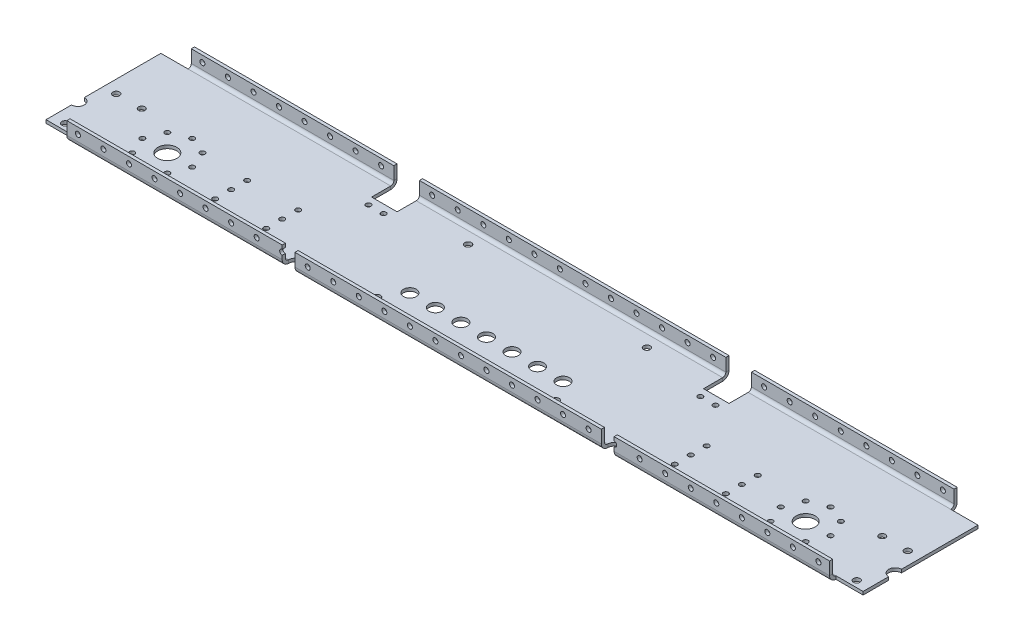
SolidWorks part; units mm, degrees
note: The reader was unsure of these and kept them because the rebuilt part matched: thickness of "Base-Flange1", "Edge-Flange1", "Sheet-Metal1", "Sheet-Metal2", "Sheet-Metal9", "Sheet-Metal10", "Sheet-Metal11", "Sheet-Metal12", "Sheet-Metal13", "Sheet-Metal14", "Sheet-Metal15", "Sheet-Metal16", "Sheet-Metal17", "Sheet-Metal18", "Sheet-Metal19", "Sheet-Metal20", "Sheet-Metal21"; flange length of "Edge-Flange1".
ref_plane "Front Plane" through (0, 0, 0) normal (0, 0, 1) x (1, 0, 0)
ref_plane "Top Plane" through (0, 0, 0) normal (0, 1, 0) x (1, 0, 0)
ref_plane "Right Plane" through (0, 0, 0) normal (1, 0, 0) x (0, 0, -1)
sketch "Sketch1" plane through (0, 0, 0) normal (0, 1, 0) x (1, 0, 0)
  line L1 (406.4, -63.5) -> (-406.4, -63.5)
  line L2 (406.4, -63.5) -> (406.4, 63.5)
  line L3 (406.4, 63.5) -> (-406.4, 63.5)
  line L4 (-406.4, -63.5) -> (-406.4, 63.5)
  line L5 (406.4, -63.5) -> (-406.4, 63.5) construction
  line L6 (406.4, 63.5) -> (-406.4, -63.5) construction
  point P0 (0, 0)
  dimension "D1" = 127
  dimension "D2" = 812.8
base flange "Base-Flange1" sketch "Sketch1" thickness 3.175 reverse thickness direction no parameters "D1"=1
edge flange "Edge-Flange1" sketch "Sketch23" flange profiles "Sketch23", "Sketch25" flange angle 90 flange length 19.05 flange position material inside bend radius 3.175 thickness 3.175 relief rectangular parameters "D6"=10, "D8"=1
bend "EdgeBend1" bend radius 3.175 bend angle 90 parameters "D5"=1
bend "EdgeBend2" bend radius 3.175 bend angle 90 parameters "D5"=2
sketch "Sketch23" plane through (0, 0, -63.5) normal (0, 0, -1) x (-1, 0, 0)
  line L0 (-406.4, 0) -> (406.4, 0) construction
  line L1 (-406.4, 0) -> (406.4, 0)
  line L2 (-406.4, 0) -> (-406.4, 15.875)
  line L3 (-406.4, 15.875) -> (406.4, 15.875)
  line L4 (406.4, 15.875) -> (406.4, 0)
sketch "Sketch25" plane through (0, 0, 63.5) normal (0, 0, 1) x (1, 0, 0)
  line L0 (-406.4, 0) -> (406.4, 0) construction
  line L1 (-406.4, 0) -> (406.4, 0)
  line L2 (-406.4, 0) -> (-406.4, 15.875)
  line L3 (-406.4, 15.875) -> (406.4, 15.875)
  line L4 (406.4, 15.875) -> (406.4, 0)
hole_wizard "Mounting Holes" positions "Sketch19" profile "Sketch20" hole size "Ø5.0" standard "ANSI Metric" end condition through all
sketch "Sketch19" plane through (342.9, 0, -63.5) normal (0, 0, 1) x (1, 0, 0)
  line L0 (63.5, 9.525) -> (-749.3, 9.525) construction
  line L3 (63.5, 15.875) -> (63.5, 3.175) construction
  point P9 (-736.6, 9.525)
  dimension "D1" = 12.7
sketch "Sketch20" plane through (-393.7, 9.525, -63.5) normal (1, 0, 0) x (0, 1, 0)
  line L0 (0, 0) -> (0, 127)
  line L1 (0, 127) -> (2.5, 127)
  line L2 (2.5, 127) -> (2.5, 0)
  line L5 (2.5, 0) -> (0, 0)
  line L11 (0, -6.35) -> (0, 107.95) construction
  dimension "Thru Hole Dia." = 5
  dimension "Thru Hole Depth" = 127
pattern_linear "LPattern3" count 32 spacing 25.4 along (1, 0, 0) of "Mounting Holes"
sketch "Sketch21" plane through (0, -3.175, 0) normal (0, -1, 0) x (1, 0, 0)
  line L0 (406.4, 0) -> (177.8, 0) construction
  line L1 (406.4, 63.5) -> (-406.4, 63.5) construction
  line L2 (-406.4, -57.15) -> (-379.349, -57.15)
  line L3 (177.8, -38.1) -> (152.4, -38.1)
  line L4 (177.8, -38.1) -> (177.8, -63.5)
  line L5 (177.8, -63.5) -> (152.4, -63.5)
  line L6 (152.4, -38.1) -> (152.4, -63.5)
  line L7 (-177.8, 0) -> (-406.4, 0) construction
  line L8 (-152.4, -63.5) -> (-177.8, -63.5)
  line L9 (-152.4, -63.5) -> (-152.4, -38.1)
  line L10 (-152.4, -38.1) -> (-177.8, -38.1)
  line L11 (-177.8, -63.5) -> (-177.8, -38.1)
  line L12 (-406.4, -57.15) -> (-406.4, 57.15) construction
  line L13 (406.4, 57.15) -> (406.4, -57.15) construction
  line L14 (-406.4, -63.5) -> (406.4, -63.5) construction
  line L16 (-406.4, -57.15) -> (-406.4, -63.5)
  line L17 (-406.4, -63.5) -> (-379.349, -63.5)
  line L18 (-379.349, -57.15) -> (-379.349, -63.5)
  line L19 (-406.4, 57.15) -> (-379.349, 57.15)
  line L20 (-406.4, 57.15) -> (-406.4, 63.5)
  line L21 (-406.4, 63.5) -> (-379.349, 63.5)
  line L22 (-379.349, 57.15) -> (-379.349, 63.5)
  line L23 (379.349, -57.15) -> (379.349, 57.15) construction
  line L24 (406.4, -57.15) -> (379.349, -57.15)
  line L25 (406.4, -57.15) -> (406.4, -63.5)
  line L26 (406.4, -63.5) -> (379.349, -63.5)
  line L27 (379.349, -57.15) -> (379.349, -63.5)
  line L28 (406.4, 57.15) -> (379.349, 57.15)
  line L29 (406.4, 57.15) -> (406.4, 63.5)
  line L30 (406.4, 63.5) -> (379.349, 63.5)
  line L31 (379.349, 57.15) -> (379.349, 63.5)
  dimension "D1" = 228.6
  dimension "D2" = 27.051
  dimension "D3" = 25.4
  dimension "D4" = 25.4
extrude "Cut-Extrude3" cut sketch "Sketch21" against normal through all normal cut yes
sketch "Sketch26" plane through (0, 0, 0) normal (0, 1, 0) x (1, 0, 0)
  line L0 (379.349, -57.15) -> (-379.349, -57.15) construction
  line L1 (152.4, -57.15) -> (152.4, -63.5)
  line L2 (379.349, -63.5) -> (-379.349, -63.5) construction
  line L3 (152.4, -63.5) -> (165.1, -63.5)
  line L4 (165.1, -63.5) -> (165.1, -57.15)
  line L5 (-165.1, -57.15) -> (-165.1, -63.5)
  line L6 (-165.1, -63.5) -> (-152.4, -63.5)
  line L7 (-152.4, -63.5) -> (-152.4, -57.15)
  line L12 (0, 158.0045) -> (0, -158.0045) construction
  line L13 (152.4, -63.5) -> (-152.4, -63.5) construction
  arc A0 (-165.1, -57.15) -> (-152.4, -57.15) centre (-158.75, -57.15) cw
  arc A1 (152.4, -57.15) -> (165.1, -57.15) centre (158.75, -57.15) cw
  point P26 (0, 0)
  point P29 (0, -63.5)
  dimension "D2" = 6.35
  dimension "D1" = 304.8
extrude "Cut-Extrude4" cut sketch "Sketch26" against normal through all both and the other way through all
hole_wizard "80/20 Connection Holes" positions "Sketch27" profile "Sketch28" hole size "Ø6.0" standard "ANSI Metric" end condition through all
sketch "Sketch27" plane through (0, 0, 0) normal (0, 1, 0) x (1, 0, 0)
  line L1 (-393.7, 0) -> (-393.7, -50.8) construction
  line L3 (393.7, -50.8) -> (393.7, 0) construction
  line L4 (406.4, -57.15) -> (406.4, 57.15) construction
  line L5 (393.7, -25.4) -> (406.4, -25.4) construction
  line L7 (-393.7, -25.4) -> (-406.4, -25.4) construction
  line L8 (-406.4, 57.15) -> (-406.4, -57.15) construction
  line L10 (393.7, -50.8) -> (393.7, -57.15) construction
  line L11 (379.349, -57.15) -> (165.1, -57.15) construction
  line L13 (-393.7, -50.8) -> (-393.7, -57.15) construction
  line L14 (-165.1, -57.15) -> (-379.349, -57.15) construction
  line L15 (406.4, -57.15) -> (379.349, -57.15) construction
  point P10 (-393.7, 0)
  point P11 (-393.7, -50.8)
  point P14 (393.7, -50.8)
  point P15 (393.7, 0)
  dimension "D1" = 31.75
  dimension "D5" = 12.7
  dimension "D6" = 50.8
sketch "Sketch28" plane through (-393.7, 0, 0) normal (1, 0, 0) x (0, 0, 1)
  line L0 (0, 0) -> (0, 3.175)
  line L1 (0, 3.175) -> (3.3, 3.175)
  line L2 (3.3, 3.175) -> (3.3, 0)
  line L5 (3.3, 0) -> (0, 0)
  line L11 (0, -6.35) -> (0, 107.95) construction
  dimension "Thru Hole Dia." = 6.6
  dimension "Thru Hole Depth" = 3.175
hole_wizard "Motor Holes" positions "Sketch29" profile "Sketch30" hole size "3/4" standard "ANSI Inch" end condition through all
sketch "Sketch29" plane through (0, 0, 0) normal (0, 1, 0) x (1, 0, 0)
  line L0 (-165.1, -63.5) -> (-379.349, -63.5) construction
  line L1 (-317.5, -25.4) -> (317.5, -25.4) construction
  line L3 (0, 0) -> (0, -25.4) construction
  line L5 (-406.4, 57.15) -> (-406.4, -57.15) construction
  point P0 (-317.5, -25.4)
  point P2 (317.5, -25.4)
  dimension "D1" = 38.1
  dimension "D2" = 88.9
sketch "Sketch30" plane through (-317.5, 0, 25.4) normal (1, 0, 0) x (0, 0, 1)
  line L0 (0, 0) -> (0, 3.175)
  line L1 (0, 3.175) -> (9.525, 3.175)
  line L2 (9.525, 3.175) -> (9.525, 0)
  line L5 (9.525, 0) -> (0, 0)
  line L11 (0, -6.35) -> (0, 107.95) construction
  dimension "Thru Hole Dia." = 19.05
  dimension "Thru Hole Depth" = 3.175
hole_wizard "1/2 (0.5) Diameter Hole1" positions "Sketch31" profile "Sketch32" hole size "1/2" standard "ANSI Inch" end condition through all
sketch "Sketch31" plane through (0, 0, 0) normal (0, 1, 0) x (1, 0, 0)
  line L0 (0, 0) -> (0, -25.4) construction
  line L2 (0, -25.4) -> (-25.4, -25.4) construction
  line L3 (-25.4, -25.4) -> (-50.8, -25.4) construction
  line L4 (-50.8, -25.4) -> (-76.2, -25.4) construction
  line L6 (0, -25.4) -> (25.4, -25.4) construction
  line L7 (25.4, -25.4) -> (50.8, -25.4) construction
  line L8 (50.8, -25.4) -> (76.2, -25.4) construction
  line L9 (152.4, -63.5) -> (-152.4, -63.5) construction
  point P2 (0, -25.4)
  point P8 (-25.4, -25.4)
  point P10 (-50.8, -25.4)
  point P12 (-76.2, -25.4)
  point P17 (25.4, -25.4)
  point P19 (50.8, -25.4)
  point P21 (76.2, -25.4)
  dimension "D1" = 25.4
  dimension "D2" = 38.1
sketch "Sketch32" plane through (76.2, 0, 25.4) normal (1, 0, 0) x (0, 0, 1)
  line L0 (0, 0) -> (0, 3.175)
  line L1 (0, 3.175) -> (6.35, 3.175)
  line L2 (6.35, 3.175) -> (6.35, 0)
  line L5 (6.35, 0) -> (0, 0)
  line L11 (0, -6.35) -> (0, 107.95) construction
  dimension "Thru Hole Dia." = 12.7
  dimension "Thru Hole Depth" = 3.175
sketch "Sketch33" plane through (0, 0, 0) normal (0, 1, 0) x (1, 0, 0)
  line L0 (-406.4, -63.5) -> (-406.4, -25.4) construction
  line L1 (-406.4, 57.15) -> (-406.4, -57.15) construction
  line L2 (-406.4, -19.05) -> (-406.4, -31.75)
  line L3 (406.4, -63.5) -> (406.4, -25.4) construction
  line L4 (406.4, -57.15) -> (406.4, 57.15) construction
  line L5 (406.4, -19.05) -> (406.4, -31.75)
  line L6 (-406.4, -63.5) -> (-379.349, -63.5) construction
  line L7 (379.349, -63.5) -> (406.4, -63.5) construction
  arc A0 (-406.4, -19.05) -> (-406.4, -31.75) centre (-406.4, -25.4) cw
  arc A1 (406.4, -19.05) -> (406.4, -31.75) centre (406.4, -25.4) ccw
  dimension "D1" = 6.35
  dimension "D2" = 38.1
extrude "Cut-Extrude5" cut sketch "Sketch33" against normal through all
hole_wizard "Churrow Holes" positions "Sketch34" profile "Sketch35" hole size "Ø1.0" standard "ANSI Metric" end condition through all
sketch "Sketch34" plane through (0, 0, 0) normal (0, 1, 0) x (1, 0, 0)
  line L0 (-165.1, 50.8) -> (-88.9, 50.8) construction
  line L1 (-88.9, 50.8) -> (-88.9, -63.5) construction
  line L3 (152.4, -63.5) -> (-152.4, -63.5) construction
  line L4 (165.1, 50.8) -> (88.9, 50.8) construction
  line L5 (88.9, 50.8) -> (88.9, -63.5) construction
  line L6 (-88.9, 45.28) -> (88.9, 45.28) construction
  line L8 (-88.9, -45.28) -> (88.9, -45.28) construction
  line L9 (-152.4, 63.5) -> (152.4, 63.5) construction
  line L10 (-165.1, 50.8) -> (-165.1, 38.1) construction
  line L11 (-177.8, 38.1) -> (-152.4, 38.1) construction
  line L13 (165.1, 50.8) -> (165.1, 38.1) construction
  line L14 (152.4, 38.1) -> (177.8, 38.1) construction
  point P16 (-88.9, 45.28)
  point P18 (-88.9, -45.28)
  point P22 (88.9, 45.28)
  point P25 (88.9, -45.28)
  dimension "D1" = 76.2
  dimension "D2" = 18.22
  dimension "D3" = 18.22
sketch "Sketch35" plane through (88.9, 0, 45.28) normal (1, 0, 0) x (0, 0, 1)
  line L0 (0, 0) -> (0, 3.175)
  line L1 (0, 3.175) -> (3.3, 3.175)
  line L2 (3.3, 3.175) -> (3.3, 0)
  line L5 (3.3, 0) -> (0, 0)
  line L11 (0, -6.35) -> (0, 107.95) construction
  dimension "Thru Hole Dia." = 6.6
  dimension "Thru Hole Depth" = 3.175
hole_wizard "80/20 Support Holes" positions "Sketch40" profile "Sketch39" hole size "Ø5.0" standard "ANSI Metric" end condition through all
sketch "Sketch40" plane through (0, 0, 0) normal (0, 1, 0) x (1, 0, 0)
  line L0 (-165.1, 50.8) -> (-165.1, 29.8) construction
  line L2 (-172.6, 29.8) -> (-157.6, 29.8) construction
  line L4 (157.6, 29.8) -> (172.6, 29.8) construction
  line L5 (165.1, 29.8) -> (165.1, 50.8) construction
  point P6 (-172.6, 29.8)
  point P7 (-157.6, 29.8)
  point P10 (-165.1, 29.8)
  point P11 (157.6, 29.8)
  point P12 (172.6, 29.8)
  dimension "D1" = 15
  dimension "D2" = 21
sketch "Sketch39" plane through (172.6, 0, -29.8) normal (1, 0, 0) x (0, 0, 1)
  line L0 (0, 0) -> (0, 3.175)
  line L1 (0, 3.175) -> (2.5, 3.175)
  line L2 (2.5, 3.175) -> (2.5, 0)
  line L5 (2.5, 0) -> (0, 0)
  line L11 (0, -6.35) -> (0, 107.95) construction
  dimension "Thru Hole Dia." = 5
  dimension "Thru Hole Depth" = 3.175
hole_wizard "Motor Gearbox Mounts" positions "Sketch43" profile "Sketch42" hole size "Ø5.0" standard "ANSI Metric"
sketch "Sketch43" plane through (0, 0, 0) normal (0, 1, 0) x (1, 0, 0)
  line L17 (317.5, -25.4) -> (317.5, -0.65) construction
  line L20 (317.5, -0.65) -> (299.9991, -7.8991) construction
  line L21 (299.9991, -7.8991) -> (292.75, -25.4) construction
  line L22 (292.75, -25.4) -> (299.9991, -42.9009) construction
  line L23 (299.9991, -42.9009) -> (317.5, -50.15) construction
  line L24 (317.5, -50.15) -> (335.0009, -42.9009) construction
  line L25 (335.0009, -42.9009) -> (342.25, -25.4) construction
  line L26 (342.25, -25.4) -> (335.0009, -7.8991) construction
  line L27 (335.0009, -7.8991) -> (317.5, -0.65) construction
  line L29 (-317.5, -0.65) -> (-335.0009, -7.8991) construction
  line L30 (-335.0009, -7.8991) -> (-342.25, -25.4) construction
  line L31 (-342.25, -25.4) -> (-335.0009, -42.9009) construction
  line L32 (-335.0009, -42.9009) -> (-317.5, -50.15) construction
  line L33 (-317.5, -50.15) -> (-299.9991, -42.9009) construction
  line L34 (-299.9991, -42.9009) -> (-292.75, -25.4) construction
  line L35 (-292.75, -25.4) -> (-299.9991, -7.8991) construction
  line L36 (-299.9991, -7.8991) -> (-317.5, -0.65) construction
  line L37 (-317.5, -0.65) -> (-317.5, -25.4) construction
  circle A0 centre (317.5, -25.4) radius 22.866 construction
  circle A1 centre (-317.5, -25.4) radius 22.866 construction
  point P64 (317.5, -0.65)
  point P68 (299.9991, -7.8991)
  point P69 (292.75, -25.4)
  point P70 (299.9991, -42.9009)
  point P71 (317.5, -50.15)
  point P72 (335.0009, -42.9009)
  point P73 (342.25, -25.4)
  point P74 (335.0009, -7.8991)
  point P96 (-317.5, -0.65)
  point P97 (-335.0009, -7.8991)
  point P98 (-342.25, -25.4)
  point P99 (-335.0009, -42.9009)
  point P100 (-317.5, -50.15)
  point P101 (-299.9991, -42.9009)
  point P102 (-292.75, -25.4)
  point P103 (-299.9991, -7.8991)
  dimension "D2" = 24.75
sketch "Sketch42" plane through (-299.9991, 0, 7.8991) normal (1, 0, 0) x (0, 0, 1)
  line L0 (0, 0) -> (0, 4.6762)
  line L1 (0, 4.6762) -> (2.5, 3.174)
  line L2 (2.5, 3.174) -> (2.5, 0)
  line L5 (2.5, 0) -> (0, 0)
  line L10 (0, 4.6762) -> (-2.5, 3.174) construction
  line L11 (0, -6.35) -> (0, 107.95) construction
  dimension "Hole Dia." = 5
  dimension "Hole Depth" = 3.174
  dimension "Drill Angle" = 118
hole_wizard "Ø5.0mm Dowel Hole3" positions "Sketch46" profile "Sketch45" hole size "Ø5.0" standard "ANSI Metric"
sketch "Sketch46" plane through (0, 0, 0) normal (0, 1, 0) x (1, 0, 0)
  line L0 (-292.75, -25.4) -> (-254, -25.4) construction
  line L1 (-254, -25.4) -> (-203.2, -25.4) construction
  line L3 (-254, -25.4) -> (-254, -9.525) construction
  line L4 (-254, -9.525) -> (-203.2, -9.525) construction
  line L5 (-203.2, -9.525) -> (-203.2, -25.4) construction
  line L6 (-203.2, -25.4) -> (-203.2, -41.275) construction
  line L7 (-203.2, -41.275) -> (-254, -41.275) construction
  line L8 (-254, -41.275) -> (-254, -25.4) construction
  line L9 (292.75, -25.4) -> (254, -25.4) construction
  line L10 (254, -25.4) -> (203.2, -25.4) construction
  line L11 (203.2, -25.4) -> (203.2, -9.525) construction
  line L12 (203.2, -9.525) -> (254, -9.525) construction
  line L13 (254, -9.525) -> (254, -25.4) construction
  line L14 (254, -25.4) -> (254, -41.275) construction
  line L15 (254, -41.275) -> (203.2, -41.275) construction
  line L16 (203.2, -41.275) -> (203.2, -25.4) construction
  point P2 (-254, -25.4)
  point P5 (-203.2, -25.4)
  point P9 (-254, -9.525)
  point P11 (-203.2, -9.525)
  point P14 (-203.2, -41.275)
  point P15 (-254, -41.275)
  point P33 (254, -25.4)
  point P35 (203.2, -25.4)
  point P36 (203.2, -9.525)
  point P37 (254, -9.525)
  point P39 (254, -41.275)
  point P40 (203.2, -41.275)
  dimension "D1" = 38.75
  dimension "D2" = 15.875
  dimension "D3" = 50.8
sketch "Sketch45" plane through (203.2, 0, 41.275) normal (1, 0, 0) x (0, 0, 1)
  line L0 (0, 0) -> (0, 4.6762)
  line L1 (0, 4.6762) -> (2.5, 3.174)
  line L2 (2.5, 3.174) -> (2.5, 0)
  line L5 (2.5, 0) -> (0, 0)
  line L10 (0, 4.6762) -> (-2.5, 3.174) construction
  line L11 (0, -6.35) -> (0, 107.95) construction
  dimension "Hole Dia." = 5
  dimension "Hole Depth" = 3.174
  dimension "Drill Angle" = 118
hole_wizard "1/4 (0.25) Diameter Hole1" positions "Sketch49" profile "Sketch50" hole size "1/4" standard "ANSI Inch"
sketch "Sketch49" plane through (0, -3.175, 0) normal (0, -1, 0) x (-1, 0, 0)
  line L0 (393.7, 0) -> (368.3, 0) construction
  line L1 (-393.7, 0) -> (-368.3, 0) construction
  point P2 (368.3, 0)
  point P16 (-368.3, 0)
  dimension "D1" = 25.4
sketch "Sketch50" plane through (368.3, -3.175, 0) normal (1, 0, 0) x (0, 0, -1)
  line L0 (0, 0) -> (0, 5.0817)
  line L1 (0, 5.0817) -> (3.175, 3.174)
  line L2 (3.175, 3.174) -> (3.175, 0)
  line L5 (3.175, 0) -> (0, 0)
  line L10 (0, 5.0817) -> (-3.175, 3.174) construction
  line L11 (0, -6.35) -> (0, 107.95) construction
  dimension "Hole Dia." = 6.35
  dimension "Hole Depth" = 3.174
  dimension "Drill Angle" = 118
sketch "Bend-Lines1" [suppressed] plane through (0, 0, 0) normal (0, 1, 0) x (1, 0, 0)
sketch "Bounding-Box1" [suppressed] plane through (0, 0, 0) normal (0, 1, 0) x (1, 0, 0)
sheet metal parameters "Sheet-Metal1" thickness 3.175 parameters "D1"=1, "D7"=3
flat pattern "Flat-Pattern1" [suppressed]
sketch "Bend-Lines2" plane through (0, 0, 0) normal (0, 1, 0) x (1, 0, 0)
sketch3d "Bounding-Box2" [suppressed]
  line L0 (-77.3309, 406.4, 0) -> (-77.3309, -406.4, 0) construction
  line L1 (77.3309, 406.4, 0) -> (77.3309, -406.4, 0) construction
  line L2 (-77.3309, 406.4, 0) -> (77.3309, 406.4, 0) construction
  line L3 (-77.3309, -406.4, 0) -> (77.3309, -406.4, 0) construction
sheet metal parameters "Sheet-Metal2" thickness 3.175 parameters "D1"=1, "D7"=3
flat pattern "Flat-Pattern1"
sketch "Bend-Lines2" plane through (0, 0, 0) normal (0, 1, 0) x (1, 0, 0)
  line L4 (-406.4, -60.8905) -> (406.4, -60.8905) construction
  line L5 (406.4, 60.8905) -> (-406.4, 60.8905) construction
  line L6 (-406.4, -60.8905) -> (406.4, -60.8905) construction
  line L7 (406.4, 60.8905) -> (-406.4, 60.8905) construction
  point P0 (-60.8905, 406.4)
  point P1 (-60.8905, -406.4)
  point P2 (60.8905, -406.4)
  point P3 (60.8905, 406.4)
sketch3d "Bounding-Box2" [suppressed]
  line L0 (406.4, -77.3309, 0) -> (-406.4, -77.3309, 0) construction
  line L1 (406.4, 77.3309, 0) -> (-406.4, 77.3309, 0) construction
  line L2 (406.4, -77.3309, 0) -> (406.4, 77.3309, 0) construction
  line L3 (-406.4, -77.3309, 0) -> (-406.4, 77.3309, 0) construction
bend of the flat pattern "Flatten-<EdgeBend1>1"
bend of the flat pattern "Flatten-<EdgeBend2>1"
sheet metal parameters "Sheet-Metal9" thickness 3.175 parameters "D1"=1, "D7"=3
flat pattern "Flat-Pattern1" [suppressed]
sketch "Bend-Lines2" plane through (0, 0, 0) normal (0, 1, 0) x (1, 0, 0)
  line L0 (-60.8905, 406.4) -> (-60.8905, -406.4) construction
  line L1 (60.8905, -406.4) -> (60.8905, 406.4) construction
  line L2 (-60.8905, 406.4) -> (-60.8905, -406.4) construction
  line L3 (60.8905, -406.4) -> (60.8905, 406.4) construction
sketch3d "Bounding-Box2" [suppressed]
  line L0 (-77.3309, 406.4, 0) -> (-77.3309, -406.4, 0) construction
  line L1 (77.3309, 406.4, 0) -> (77.3309, -406.4, 0) construction
  line L2 (-77.3309, 406.4, 0) -> (77.3309, 406.4, 0) construction
  line L3 (-77.3309, -406.4, 0) -> (77.3309, -406.4, 0) construction
bend of the flat pattern "Flatten-<EdgeBend2>2"
bend of the flat pattern "Flatten-<EdgeBend1>2"
sheet metal parameters "Sheet-Metal10" thickness 3.175 parameters "D1"=1, "D7"=3
flat pattern "Flat-Pattern1"
sketch "Bend-Lines2" plane through (0, 0, 0) normal (0, 1, 0) x (1, 0, 0)
  line L4 (-406.4, -60.8905) -> (406.4, -60.8905) construction
  line L5 (406.4, 60.8905) -> (-406.4, 60.8905) construction
  line L6 (-406.4, -60.8905) -> (406.4, -60.8905) construction
  line L7 (406.4, 60.8905) -> (-406.4, 60.8905) construction
sketch3d "Bounding-Box2" [suppressed]
  line L0 (406.4, -77.3309, 0) -> (-406.4, -77.3309, 0) construction
  line L1 (406.4, 77.3309, 0) -> (-406.4, 77.3309, 0) construction
  line L2 (406.4, -77.3309, 0) -> (406.4, 77.3309, 0) construction
  line L3 (-406.4, -77.3309, 0) -> (-406.4, 77.3309, 0) construction
bend of the flat pattern "Flatten-<EdgeBend2>3"
bend of the flat pattern "Flatten-<EdgeBend1>3"
sheet metal parameters "Sheet-Metal11" thickness 3.175 parameters "D1"=1, "D7"=3
flat pattern "Flat-Pattern1"
sketch "Bend-Lines2" plane through (0, 0, 0) normal (0, 1, 0) x (1, 0, 0)
  line L6 (-406.4, -60.8905) -> (406.4, -60.8905) construction
  line L7 (406.4, 60.8905) -> (-406.4, 60.8905) construction
  line L8 (-406.4, -60.8905) -> (406.4, -60.8905) construction
  line L9 (406.4, 60.8905) -> (177.8, 60.8905) construction
  line L10 (152.4, 60.8905) -> (-152.4, 60.8905) construction
  line L11 (-177.8, 60.8905) -> (-406.4, 60.8905) construction
  point P0 (-60.8905, 406.4)
  point P1 (-60.8905, -406.4)
  point P2 (60.8905, 177.8)
  point P3 (60.8905, 406.4)
sketch3d "Bounding-Box2" [suppressed]
  line L0 (406.4, -77.3309, 0) -> (-406.4, -77.3309, 0) construction
  line L1 (406.4, 77.3309, 0) -> (-406.4, 77.3309, 0) construction
  line L2 (406.4, -77.3309, 0) -> (406.4, 77.3309, 0) construction
  line L3 (-406.4, -77.3309, 0) -> (-406.4, 77.3309, 0) construction
bend of the flat pattern "Flatten-<EdgeBend2>4"
bend of the flat pattern "Flatten-<EdgeBend1>4"
sheet metal parameters "Sheet-Metal12" thickness 3.175 parameters "D1"=1, "D7"=3
flat pattern "Flat-Pattern1"
sketch "Bend-Lines2" plane through (0, 0, 0) normal (0, 1, 0) x (1, 0, 0)
  line L0 (-406.4, -60.8905) -> (-203.2, -60.8905) construction
  line L1 (-190.5, -60.8905) -> (190.5, -60.8905) construction
  line L6 (203.2, -60.8905) -> (406.4, -60.8905) construction
  line L7 (406.4, 60.8905) -> (-406.4, 60.8905) construction
  line L8 (203.2, -60.8905) -> (406.4, -60.8905) construction
  line L9 (406.4, 60.8905) -> (177.8, 60.8905) construction
  line L10 (152.4, 60.8905) -> (-152.4, 60.8905) construction
  line L11 (-177.8, 60.8905) -> (-406.4, 60.8905) construction
sketch3d "Bounding-Box2" [suppressed]
  line L0 (406.4, -77.3309, 0) -> (-406.4, -77.3309, 0) construction
  line L1 (406.4, 77.3309, 0) -> (-406.4, 77.3309, 0) construction
  line L2 (406.4, -77.3309, 0) -> (406.4, 77.3309, 0) construction
  line L3 (-406.4, -77.3309, 0) -> (-406.4, 77.3309, 0) construction
bend of the flat pattern "Flatten-<EdgeBend2>4"
bend of the flat pattern "Flatten-<EdgeBend1>4"
sheet metal parameters "Sheet-Metal13" thickness 3.175 parameters "D1"=1, "D7"=3
flat pattern "Flat-Pattern1"
sketch "Bend-Lines2" plane through (0, 0, 0) normal (0, 1, 0) x (1, 0, 0)
  line L0 (-406.4, -60.8905) -> (-203.2, -60.8905) construction
  line L1 (-190.5, -60.8905) -> (190.5, -60.8905) construction
  line L6 (203.2, -60.8905) -> (406.4, -60.8905) construction
  line L7 (406.4, 60.8905) -> (-406.4, 60.8905) construction
  line L8 (203.2, -60.8905) -> (406.4, -60.8905) construction
  line L9 (406.4, 60.8905) -> (177.8, 60.8905) construction
  line L10 (152.4, 60.8905) -> (-152.4, 60.8905) construction
  line L11 (-177.8, 60.8905) -> (-406.4, 60.8905) construction
sketch3d "Bounding-Box2" [suppressed]
  line L0 (406.4, -77.3309, 0) -> (-406.4, -77.3309, 0) construction
  line L1 (406.4, 77.3309, 0) -> (-406.4, 77.3309, 0) construction
  line L2 (406.4, -77.3309, 0) -> (406.4, 77.3309, 0) construction
  line L3 (-406.4, -77.3309, 0) -> (-406.4, 77.3309, 0) construction
bend of the flat pattern "Flatten-<EdgeBend2>4"
bend of the flat pattern "Flatten-<EdgeBend1>4"
sheet metal parameters "Sheet-Metal14" thickness 3.175 parameters "D1"=1, "D7"=3
flat pattern "Flat-Pattern1"
sketch "Bend-Lines2" plane through (0, 0, 0) normal (0, 1, 0) x (1, 0, 0)
  line L0 (-406.4, -60.8905) -> (-203.2, -60.8905) construction
  line L1 (-190.5, -60.8905) -> (190.5, -60.8905) construction
  line L6 (203.2, -60.8905) -> (406.4, -60.8905) construction
  line L7 (406.4, 60.8905) -> (-406.4, 60.8905) construction
  line L8 (203.2, -60.8905) -> (406.4, -60.8905) construction
  line L9 (406.4, 60.8905) -> (177.8, 60.8905) construction
  line L10 (152.4, 60.8905) -> (-152.4, 60.8905) construction
  line L11 (-177.8, 60.8905) -> (-406.4, 60.8905) construction
sketch3d "Bounding-Box2" [suppressed]
  line L0 (406.4, -77.3309, 0) -> (-406.4, -77.3309, 0) construction
  line L1 (406.4, 77.3309, 0) -> (-406.4, 77.3309, 0) construction
  line L2 (406.4, -77.3309, 0) -> (406.4, 77.3309, 0) construction
  line L3 (-406.4, -77.3309, 0) -> (-406.4, 77.3309, 0) construction
bend of the flat pattern "Flatten-<EdgeBend2>4"
bend of the flat pattern "Flatten-<EdgeBend1>4"
sheet metal parameters "Sheet-Metal15" thickness 3.175 parameters "D1"=1, "D7"=3
flat pattern "Flat-Pattern1"
sketch "Bend-Lines2" plane through (0, 0, 0) normal (0, 1, 0) x (1, 0, 0)
  line L0 (-406.4, -60.8905) -> (-203.2, -60.8905) construction
  line L1 (-190.5, -60.8905) -> (190.5, -60.8905) construction
  line L6 (203.2, -60.8905) -> (406.4, -60.8905) construction
  line L7 (406.4, 60.8905) -> (-406.4, 60.8905) construction
  line L8 (203.2, -60.8905) -> (406.4, -60.8905) construction
  line L9 (406.4, 60.8905) -> (177.8, 60.8905) construction
  line L10 (152.4, 60.8905) -> (-152.4, 60.8905) construction
  line L11 (-177.8, 60.8905) -> (-406.4, 60.8905) construction
sketch3d "Bounding-Box2" [suppressed]
  line L0 (406.4, -77.3309, 0) -> (-406.4, -77.3309, 0) construction
  line L1 (406.4, 77.3309, 0) -> (-406.4, 77.3309, 0) construction
  line L2 (406.4, -77.3309, 0) -> (406.4, 77.3309, 0) construction
  line L3 (-406.4, -77.3309, 0) -> (-406.4, 77.3309, 0) construction
bend of the flat pattern "Flatten-<EdgeBend2>4"
bend of the flat pattern "Flatten-<EdgeBend1>4"
sheet metal parameters "Sheet-Metal16" thickness 3.175 parameters "D1"=1, "D7"=3
flat pattern "Flat-Pattern1"
sketch "Bend-Lines2" plane through (0, 0, 0) normal (0, 1, 0) x (1, 0, 0)
  line L0 (-190.5, -60.8905) -> (190.5, -60.8905) construction
  line L1 (203.2, -60.8905) -> (406.4, -60.8905) construction
  line L6 (-406.4, -60.8905) -> (-203.2, -60.8905) construction
  line L7 (406.4, 60.8905) -> (-406.4, 60.8905) construction
  line L8 (-406.4, -60.8905) -> (-203.2, -60.8905) construction
  line L9 (406.4, 60.8905) -> (177.8, 60.8905) construction
  line L10 (152.4, 60.8905) -> (-152.4, 60.8905) construction
  line L11 (-177.8, 60.8905) -> (-406.4, 60.8905) construction
sketch3d "Bounding-Box2" [suppressed]
  line L0 (406.4, -77.3309, 0) -> (-406.4, -77.3309, 0) construction
  line L1 (406.4, 77.3309, 0) -> (-406.4, 77.3309, 0) construction
  line L2 (406.4, -77.3309, 0) -> (406.4, 77.3309, 0) construction
  line L3 (-406.4, -77.3309, 0) -> (-406.4, 77.3309, 0) construction
bend of the flat pattern "Flatten-<EdgeBend2>4"
bend of the flat pattern "Flatten-<EdgeBend1>4"
sheet metal parameters "Sheet-Metal17" thickness 3.175 parameters "D1"=1, "D7"=3
flat pattern "Flat-Pattern1"
sketch "Bend-Lines2" plane through (0, 0, 0) normal (0, 1, 0) x (1, 0, 0)
  line L0 (-190.5, -60.8905) -> (190.5, -60.8905) construction
  line L1 (203.2, -60.8905) -> (406.4, -60.8905) construction
  line L6 (-406.4, -60.8905) -> (-203.2, -60.8905) construction
  line L7 (406.4, 60.8905) -> (-406.4, 60.8905) construction
  line L8 (-406.4, -60.8905) -> (-203.2, -60.8905) construction
  line L9 (406.4, 60.8905) -> (177.8, 60.8905) construction
  line L10 (152.4, 60.8905) -> (-152.4, 60.8905) construction
  line L11 (-177.8, 60.8905) -> (-406.4, 60.8905) construction
sketch3d "Bounding-Box2" [suppressed]
  line L0 (406.4, -77.3309, 0) -> (-406.4, -77.3309, 0) construction
  line L1 (406.4, 77.3309, 0) -> (-406.4, 77.3309, 0) construction
  line L2 (406.4, -77.3309, 0) -> (406.4, 77.3309, 0) construction
  line L3 (-406.4, -77.3309, 0) -> (-406.4, 77.3309, 0) construction
bend of the flat pattern "Flatten-<EdgeBend2>4"
bend of the flat pattern "Flatten-<EdgeBend1>4"
sheet metal parameters "Sheet-Metal18" thickness 3.175 parameters "D1"=1, "D7"=3
flat pattern "Flat-Pattern1"
sketch "Bend-Lines2" plane through (0, 0, 0) normal (0, 1, 0) x (1, 0, 0)
  line L0 (-152.4, -60.8905) -> (152.4, -60.8905) construction
  line L1 (165.1, -60.8905) -> (379.349, -60.8905) construction
  line L6 (-379.349, -60.8905) -> (-165.1, -60.8905) construction
  line L7 (379.349, 60.8905) -> (-379.349, 60.8905) construction
  line L8 (-379.349, -60.8905) -> (-165.1, -60.8905) construction
  line L9 (379.349, 60.8905) -> (177.8, 60.8905) construction
  line L10 (152.4, 60.8905) -> (-152.4, 60.8905) construction
  line L11 (-177.8, 60.8905) -> (-379.349, 60.8905) construction
sketch3d "Bounding-Box2" [suppressed]
  line L0 (406.4, -77.3309, 0) -> (-406.4, -77.3309, 0) construction
  line L1 (406.4, 77.3309, 0) -> (-406.4, 77.3309, 0) construction
  line L2 (406.4, -77.3309, 0) -> (406.4, 77.3309, 0) construction
  line L3 (-406.4, -77.3309, 0) -> (-406.4, 77.3309, 0) construction
bend of the flat pattern "Flatten-<EdgeBend2>4"
bend of the flat pattern "Flatten-<EdgeBend1>4"
sheet metal parameters "Sheet-Metal19" thickness 3.175 parameters "D1"=1, "D7"=3
flat pattern "Flat-Pattern1"
sketch "Bend-Lines2" plane through (0, 0, 0) normal (0, 1, 0) x (1, 0, 0)
  line L0 (-152.4, -60.8905) -> (152.4, -60.8905) construction
  line L1 (165.1, -60.8905) -> (379.349, -60.8905) construction
  line L6 (-379.349, -60.8905) -> (-165.1, -60.8905) construction
  line L7 (379.349, 60.8905) -> (-379.349, 60.8905) construction
  line L8 (-379.349, -60.8905) -> (-165.1, -60.8905) construction
  line L9 (379.349, 60.8905) -> (177.8, 60.8905) construction
  line L10 (152.4, 60.8905) -> (-152.4, 60.8905) construction
  line L11 (-177.8, 60.8905) -> (-379.349, 60.8905) construction
sketch3d "Bounding-Box2" [suppressed]
  line L0 (406.4, -77.3309, 0) -> (-406.4, -77.3309, 0) construction
  line L1 (406.4, 77.3309, 0) -> (-406.4, 77.3309, 0) construction
  line L2 (406.4, -77.3309, 0) -> (406.4, 77.3309, 0) construction
  line L3 (-406.4, -77.3309, 0) -> (-406.4, 77.3309, 0) construction
bend of the flat pattern "Flatten-<EdgeBend2>4"
bend of the flat pattern "Flatten-<EdgeBend1>4"
sheet metal parameters "Sheet-Metal20" thickness 3.175 parameters "D1"=1, "D7"=3
flat pattern "Flat-Pattern1"
sketch "Bend-Lines2" plane through (0, 0, 0) normal (0, 1, 0) x (1, 0, 0)
  line L0 (-152.4, -60.8905) -> (152.4, -60.8905) construction
  line L1 (165.1, -60.8905) -> (379.349, -60.8905) construction
  line L6 (-379.349, -60.8905) -> (-165.1, -60.8905) construction
  line L7 (379.349, 60.8905) -> (-379.349, 60.8905) construction
  line L8 (-379.349, -60.8905) -> (-165.1, -60.8905) construction
  line L9 (379.349, 60.8905) -> (177.8, 60.8905) construction
  line L10 (152.4, 60.8905) -> (-152.4, 60.8905) construction
  line L11 (-177.8, 60.8905) -> (-379.349, 60.8905) construction
sketch3d "Bounding-Box2" [suppressed]
  line L0 (406.4, -77.3309, 0) -> (-406.4, -77.3309, 0) construction
  line L1 (406.4, 77.3309, 0) -> (-406.4, 77.3309, 0) construction
  line L2 (406.4, -77.3309, 0) -> (406.4, 77.3309, 0) construction
  line L3 (-406.4, -77.3309, 0) -> (-406.4, 77.3309, 0) construction
bend of the flat pattern "Flatten-<EdgeBend2>4"
bend of the flat pattern "Flatten-<EdgeBend1>4"
sheet metal parameters "Sheet-Metal21" thickness 3.175 parameters "D1"=1, "D7"=3
flat pattern "Flat-Pattern1"
sketch "Bend-Lines2" plane through (0, 0, 0) normal (0, 1, 0) x (1, 0, 0)
  line L0 (-152.4, -60.8905) -> (152.4, -60.8905) construction
  line L1 (165.1, -60.8905) -> (379.349, -60.8905) construction
  line L6 (-379.349, -60.8905) -> (-165.1, -60.8905) construction
  line L7 (379.349, 60.8905) -> (-379.349, 60.8905) construction
  line L8 (-379.349, -60.8905) -> (-165.1, -60.8905) construction
  line L9 (379.349, 60.8905) -> (177.8, 60.8905) construction
  line L10 (152.4, 60.8905) -> (-152.4, 60.8905) construction
  line L11 (-177.8, 60.8905) -> (-379.349, 60.8905) construction
sketch3d "Bounding-Box2" [suppressed]
  line L0 (406.4, -77.3309, 0) -> (-406.4, -77.3309, 0) construction
  line L1 (406.4, 77.3309, 0) -> (-406.4, 77.3309, 0) construction
  line L2 (406.4, -77.3309, 0) -> (406.4, 77.3309, 0) construction
  line L3 (-406.4, -77.3309, 0) -> (-406.4, 77.3309, 0) construction
bend of the flat pattern "Flatten-<EdgeBend2>4"
bend of the flat pattern "Flatten-<EdgeBend1>4"
